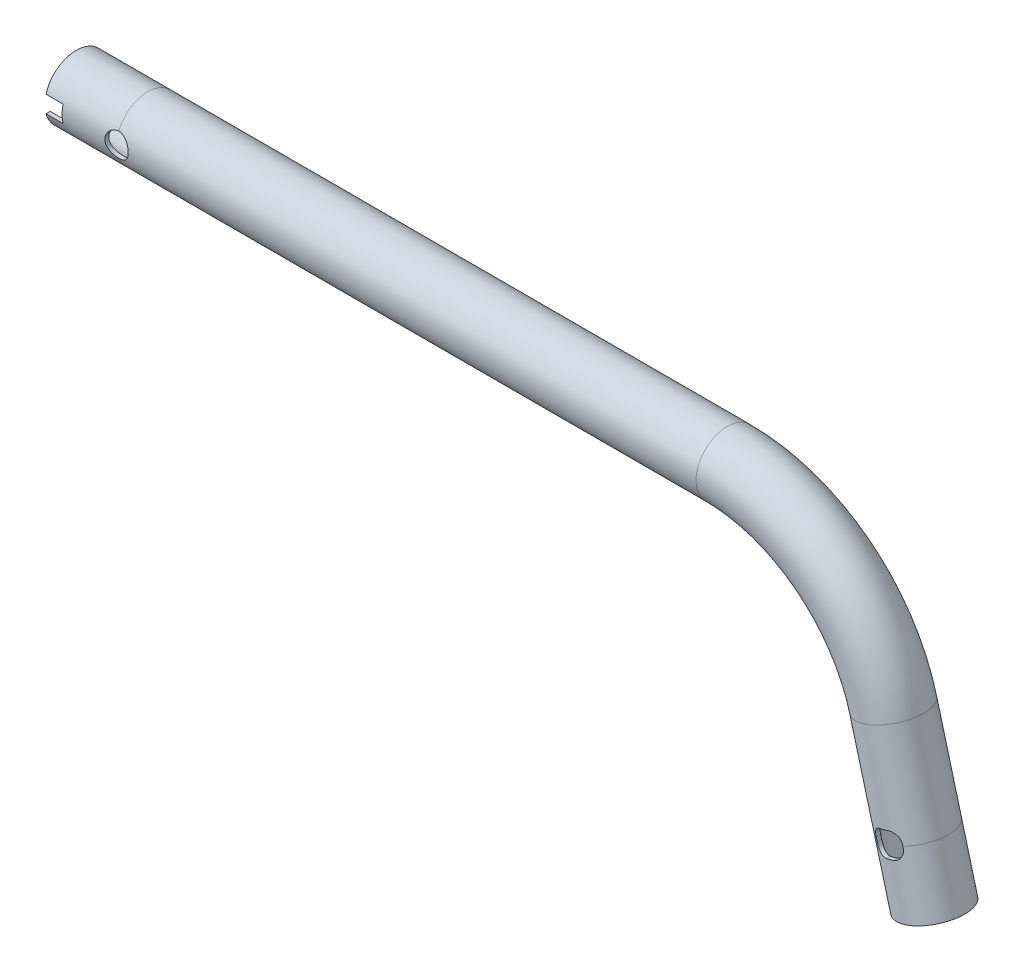
SolidWorks part; units mm, degrees
ref_plane "Front Plane" through (0, 0, 0) normal (0, 0, 1) x (1, 0, 0)
ref_plane "Top Plane" through (0, 0, 0) normal (0, 1, 0) x (1, 0, 0)
ref_plane "Right Plane" through (0, 0, 0) normal (1, 0, 0) x (0, 0, -1)
sketch "Sketch1" plane through (0, 0, 0) normal (0, 0, 1) x (1, 0, 0)
  line L0 (0, 0) -> (175.5036, 0)
  line L1 (225.7317, -38.5414) -> (233.25, -66.6)
  line L2 (0, 0) -> (-21.7, 0)
  line L3 (233.25, -66.6) -> (238.1803, -85)
  arc A0 (225.7317, -38.5414) -> (175.5036, 0) centre (175.5036, -52) ccw
  point P10 (233.25, -66.6)
  dimension "D2" = 52
  dimension "D1" = 75
  dimension "D3" = 233.25
  dimension "D4" = 66.6
  dimension "D5" = 21.7
  dimension "D6" = 85
ref_plane "Plane1" through (-21.7, 0, 0) normal (-1, 0, 0) x (0, 0, 1)
sketch "Sketch2" plane through (-21.7, 0, 0) normal (-1, 0, 0) x (0, 0, 1)
  circle A0 centre (0, 0) radius 9.5
  circle A1 centre (0, 0) radius 8.3
  dimension "D1" = 1.2
sweep "Sweep1" add profiles "Sketch2" path "Sketch1"
sketch "Sketch3" plane through (0, 0, 0) normal (0, 0, 1) x (1, 0, 0)
  line L2 (233.1153, -70.3475) -> (235.2404, -69.7781)
  line L3 (231.2596, -63.4219) -> (233.3847, -62.8525)
  line L4 (229.1383, -67.0961) -> (229.4411, -68.2262)
  line L6 (237.0589, -64.9738) -> (237.3617, -66.1039)
  arc A5 (233.1153, -70.3475) -> (229.4411, -68.2262) centre (232.3389, -67.4498) cw
  arc A6 (235.2404, -69.7781) -> (237.3617, -66.1039) centre (234.4639, -66.8804) ccw
  arc A7 (233.3847, -62.8525) -> (237.0589, -64.9738) centre (234.1611, -65.7502) cw
  arc A8 (231.2596, -63.4219) -> (229.1383, -67.0961) centre (232.0361, -66.3196) ccw
  point P7 (233.25, -66.6)
  dimension "D1" = 3
  dimension "D2" = 3
extrude "Cut-Extrude1" cut sketch "Sketch3" against normal up to next and the other way up to next
sketch "Sketch4" plane through (0, 0, 0) normal (0, 0, 1) x (1, 0, 0)
  line L0 (0, -9.5) -> (0, 9.5) construction
  circle A0 centre (0, 0) radius 3.55
  dimension "D1" = 7.1
extrude "Cut-Extrude2" cut sketch "Sketch4" along normal up to next
sketch "Sketch5" plane through (0, 0, 0) normal (0, 0, 1) x (1, 0, 0)
  line L0 (-21.7, 0) -> (-21.7, 2.555)
  line L1 (-21.7, 9.5) -> (-21.7, -9.5) construction
  line L2 (-21.7, 2.555) -> (-16.5, 2.555)
  line L3 (-16.5, 2.555) -> (-16.5, -2.555)
  line L4 (-16.5, -2.555) -> (-21.7, -2.555)
  line L5 (-21.7, -2.555) -> (-21.7, 0)
  dimension "D1" = 5.2
  dimension "D2" = 5.11
extrude "Cut-Extrude3" cut sketch "Sketch5" against normal through all and the other way through all
